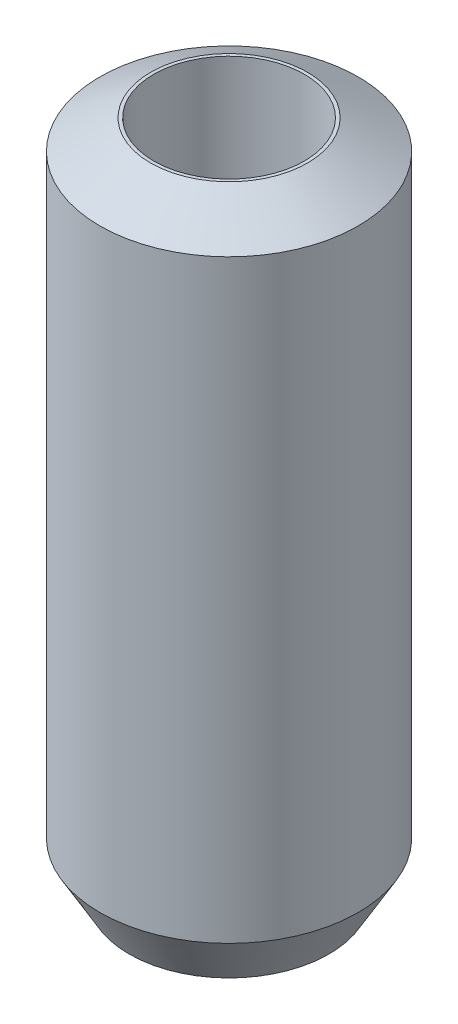
SolidWorks part; units mm, degrees
ref_plane "Front Plane" through (0, 0, 0) normal (0, 0, 1) x (1, 0, 0)
ref_plane "Top Plane" through (0, 0, 0) normal (0, 1, 0) x (1, 0, 0)
ref_plane "Right Plane" through (0, 0, 0) normal (1, 0, 0) x (0, 0, -1)
sketch "Sketch1" plane through (0, 0, 0) normal (0, 1, 0) x (1, 0, 0)
  circle A0 centre (0, 0) radius 12.5
  dimension "SHAFT_OD" = 25
extrude "Boss-Extrude1" add sketch "Sketch1" along normal blind 65.2756
sketch "Sketch2" plane through (0, 0, 0) normal (0, 1, 0) x (1, 0, 0)
  circle A0 centre (0, 0) radius 7.2865
  dimension "BORE_D" = 14.573
extrude "Cut-Extrude1" cut sketch "Sketch2" along normal through all
chamfer "Chamfer1" distance 2.8274 angle 60 2 edges at (0, 65.2756, 12.5) (0, 0, 12.5) first distance on face at (0, 65.2756, 12.5) first distance on face at (0, 0, 7.2865)
